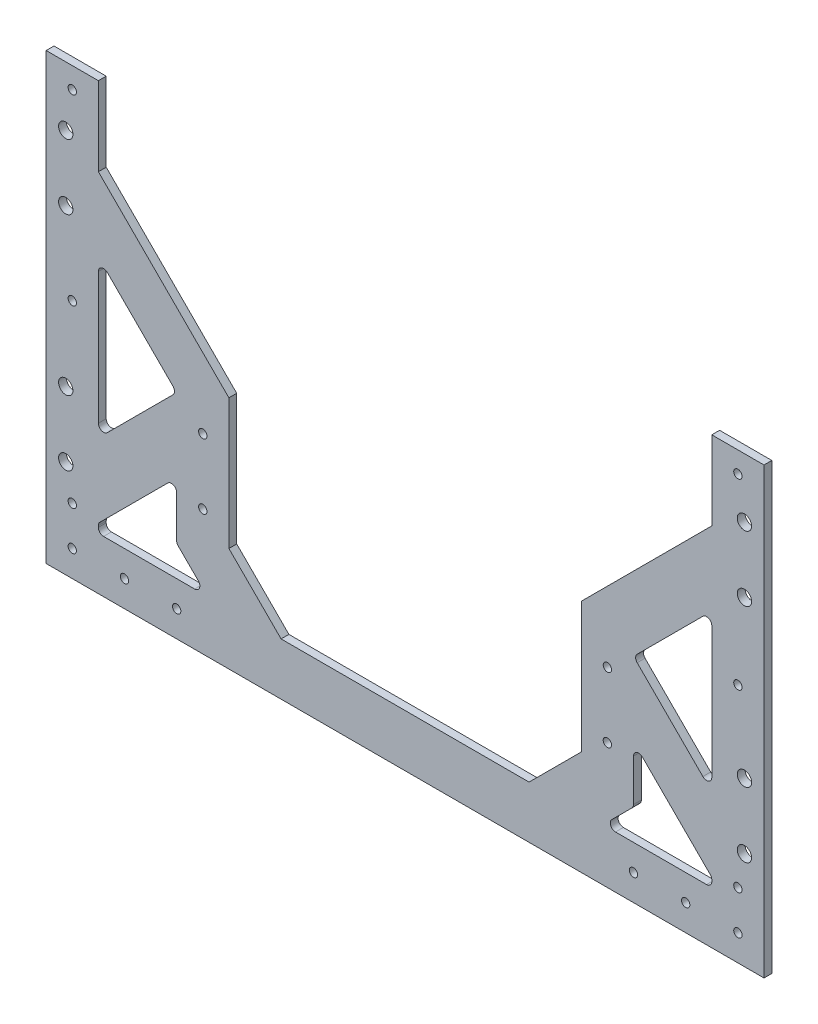
SolidWorks part; units mm, degrees
material "Thornel Mat VMA"
ref_plane "Front Plane" through (0, 0, 0) normal (0, 0, 1) x (1, 0, 0)
ref_plane "Top Plane" through (0, 0, 0) normal (0, 1, 0) x (1, 0, 0)
ref_plane "Right Plane" through (0, 0, 0) normal (1, 0, 0) x (0, 0, -1)
sketch "Sketch1" plane through (0, 0, 0) normal (0, 0, 1) x (1, 0, 0)
  line L0 (-21.5101, 142.7096) -> (-21.5101, -27.503)
  line L1 (-21.5101, 592.497) -> (-21.5101, 302.497) construction
  line L2 (-171.5101, -27.503) -> (403.4899, -27.503) construction
  line L3 (-21.5101, -27.503) -> (253.4899, -27.503)
  line L4 (253.4899, -27.503) -> (253.4899, 142.7096)
  line L5 (253.4899, -7.503) -> (253.4899, 282.497) construction
  line L6 (253.4899, 142.7096) -> (233.4899, 142.7096)
  line L7 (233.4899, -7.503) -> (233.4899, 282.497) construction
  line L8 (233.4899, 142.7096) -> (233.4899, 112.497)
  line L9 (233.4899, 112.497) -> (183.4899, 62.497)
  line L10 (183.4899, 62.497) -> (183.4899, 12.497)
  line L11 (183.4899, 12.497) -> (163.4899, -7.503)
  line L12 (-1.5101, -7.503) -> (233.4899, -7.503) construction
  line L13 (163.4899, -7.503) -> (68.4899, -7.503)
  line L14 (115.9899, -7.503) -> (115.9899, 82.0954) construction
  line L15 (48.4899, 12.497) -> (68.4899, -7.503)
  line L16 (48.4899, 62.497) -> (48.4899, 12.497)
  line L17 (-1.5101, 112.497) -> (48.4899, 62.497)
  line L18 (-1.5101, 142.7096) -> (-1.5101, 112.497)
  line L19 (-21.5101, 142.7096) -> (-1.5101, 142.7096)
  line L20 (-1.5101, 592.497) -> (-1.5101, 302.497) construction
  line L21 (233.4899, -7.503) -> (233.4899, 282.497) construction
  line L22 (-1.5101, -7.503) -> (233.4899, -7.503) construction
  line L23 (-1.5101, -5.503) -> (-1.5101, -4.8999)
  line L24 (1.9041, 80.7986) -> (27.0757, 55.627)
  line L25 (28.4899, 21.1001) -> (28.4899, 5.0412)
  line L26 (29.0757, 3.627) -> (36.7914, -4.0887)
  line L27 (35.3772, -7.503) -> (0.4899, -7.503)
  line L28 (27.0757, 52.7986) -> (1.9041, 27.627)
  line L29 (233.4899, 29.0412) -> (233.4899, 79.3843)
  line L30 (-0.9243, -3.4857) -> (25.0757, 22.5143)
  line L31 (-1.5101, 29.0412) -> (-1.5101, 79.3843)
  line L32 (230.0757, 80.7986) -> (204.9041, 55.627)
  line L33 (232.9041, -3.4857) -> (206.9041, 22.5143)
  line L34 (204.9041, 52.7986) -> (230.0757, 27.627)
  line L35 (196.6026, -7.503) -> (231.4899, -7.503)
  line L36 (202.9041, 3.627) -> (195.1884, -4.0887)
  line L37 (203.4899, 21.1001) -> (203.4899, 5.0412)
  line L38 (233.4899, -5.503) -> (233.4899, -4.8999)
  arc A0 (36.7914, -4.0887) -> (35.3772, -7.503) centre (35.3772, -5.503) cw
  arc A1 (28.4899, 5.0412) -> (29.0757, 3.627) centre (30.4899, 5.0412) ccw
  arc A2 (25.0757, 22.5143) -> (28.4899, 21.1001) centre (26.4899, 21.1001) cw
  arc A3 (-1.5101, 79.3843) -> (1.9041, 80.7986) centre (0.4899, 79.3843) cw
  arc A4 (27.0757, 55.627) -> (27.0757, 52.7986) centre (25.6615, 54.2128) cw
  arc A5 (1.9041, 27.627) -> (-1.5101, 29.0412) centre (0.4899, 29.0412) cw
  arc A6 (-1.5101, -4.8999) -> (-0.9243, -3.4857) centre (0.4899, -4.8999) cw
  arc A7 (-1.5101, -5.503) -> (0.4899, -7.503) centre (0.4899, -5.503) ccw
  arc A8 (233.4899, 79.3843) -> (230.0757, 80.7986) centre (231.4899, 79.3843) ccw
  arc A9 (233.4899, -5.503) -> (231.4899, -7.503) centre (231.4899, -5.503) cw
  arc A10 (233.4899, -4.8999) -> (232.9041, -3.4857) centre (231.4899, -4.8999) ccw
  arc A11 (230.0757, 27.627) -> (233.4899, 29.0412) centre (231.4899, 29.0412) ccw
  arc A12 (204.9041, 55.627) -> (204.9041, 52.7986) centre (206.3183, 54.2128) ccw
  arc A13 (206.9041, 22.5143) -> (203.4899, 21.1001) centre (205.4899, 21.1001) ccw
  arc A14 (203.4899, 5.0412) -> (202.9041, 3.627) centre (201.4899, 5.0412) cw
  arc A15 (195.1884, -4.0887) -> (196.6026, -7.503) centre (196.6026, -5.503) ccw
  point P41 (28.4899, 4.6429)
  point P44 (40.2056, -7.503)
  point P55 (-1.5101, 24.2128)
  point P60 (-1.5101, -7.503)
  dimension "D10" = 2
  dimension "D1" = 20
  dimension "D2" = 45
  dimension "D3" = 50
  dimension "D4" = 20
  dimension "D5" = 50
  dimension "D6" = 20
  dimension "D7" = 20
  dimension "D8" = 20
  dimension "D9" = 45
extrude "Extrude1" add sketch "Sketch1" along normal blind 3
sketch "Sketch2" plane through (0, 0, 3) normal (0, 0, 1) x (1, 0, 0)
  line L0 (-11.5101, 142.7096) -> (-11.5101, -27.503) construction
  line L1 (-1.5101, 142.7096) -> (-21.5101, 142.7096) construction
  line L2 (-21.5101, -27.503) -> (253.4899, -27.503) construction
  line L3 (115.9899, -7.503) -> (115.9899, -27.503) construction
  line L4 (-1.5101, -7.503) -> (233.4899, -7.503) construction
  line L5 (-221.5101, -27.503) -> (453.4899, -27.503) construction
  line L6 (-21.5101, -17.503) -> (115.9899, -17.503) construction
  line L7 (-21.5101, 142.7096) -> (-21.5101, -27.503) construction
  line L8 (68.4899, 20.5695) -> (38.4899, 20.5695) construction
  line L9 (68.4899, 45.5695) -> (38.4899, 45.5695) construction
  line L10 (38.4899, 20.5695) -> (38.4899, 45.5695) construction
  line L11 (48.4899, 12.497) -> (48.4899, 62.497) construction
  circle A0 centre (245.9899, 9.9974) radius 2.75 construction
  circle A1 centre (245.9899, 34.9974) radius 2.75 construction
  circle A2 centre (245.9899, 94.9974) radius 2.75 construction
  circle A3 centre (245.9899, 119.9974) radius 2.75 construction
  circle A4 centre (-14.0101, 9.9974) radius 2.75 construction
  circle A5 centre (-14.0101, 34.9974) radius 2.75 construction
  circle A6 centre (-14.0101, 94.9974) radius 2.75 construction
  circle A7 centre (-14.0101, 119.9974) radius 2.75 construction
  circle A8 centre (245.9899, 9.9974) radius 2.75
  circle A9 centre (245.9899, 34.9974) radius 2.75
  circle A10 centre (245.9899, 94.9974) radius 2.75
  circle A11 centre (245.9899, 119.9974) radius 2.75
  circle A12 centre (-14.0101, 9.9974) radius 2.75
  circle A13 centre (-14.0101, 34.9974) radius 2.75
  circle A14 centre (-14.0101, 94.9974) radius 2.75
  circle A15 centre (-14.0101, 119.9974) radius 2.75
  circle A16 centre (-11.5101, 134.7096) radius 1.6
  circle A17 centre (-11.5101, 64.7096) radius 1.6
  circle A18 centre (-11.5101, -2.503) radius 1.6
  circle A19 centre (-11.5101, -17.503) radius 1.6
  circle A20 centre (8.4899, -17.503) radius 1.6
  circle A21 centre (28.4899, -17.503) radius 1.6
  circle A22 centre (203.4899, -17.503) radius 1.6
  circle A23 centre (223.4899, -17.503) radius 1.6
  circle A24 centre (243.4899, -17.503) radius 1.6
  circle A25 centre (243.4899, -2.503) radius 1.6
  circle A26 centre (243.4899, 64.7096) radius 1.6
  circle A27 centre (243.4899, 134.7096) radius 1.6
  circle A28 centre (245.9899, 119.9974) radius 2.75
  circle A29 centre (245.9899, 94.9974) radius 2.75
  circle A30 centre (245.9899, 34.9974) radius 2.75
  circle A31 centre (245.9899, 9.9974) radius 2.75
  circle A32 centre (38.4899, 20.5695) radius 1.6
  circle A33 centre (38.4899, 45.5695) radius 1.6
  circle A34 centre (193.4899, 45.5695) radius 1.6
  circle A35 centre (193.4899, 20.5695) radius 1.6
  point P82 (0, 0)
  point P83 (0, 0)
  dimension "D1" = 3.2
  dimension "D3" = 70
  dimension "D4" = 15
  dimension "D5" = 20
  dimension "D6" = 20
  dimension "D8" = 3.2
  dimension "D2" = 8
  dimension "D7" = 10
extrude "Cut-Extrude1" cut sketch "Sketch2" against normal blind 3 contours A15 | A14 | A13 | A12 | A18 | A19 | A20 | A21 | A32 | A33 | A17 | A34 | A35 | A22 | A23 | A24 | A9 | A8 | A26 | A27 | A11 | A10 | A16 | A25 region at (245.9899, 9.9974, 3) region at (245.9899, 34.9974, 3) region at (245.9899, 94.9974, 3) region at (245.9899, 119.9974, 3) region at (-14.0101, 9.9974, 3) region at (-14.0101, 34.9974, 3) region at (-14.0101, 94.9974, 3) region at (-14.0101, 119.9974, 3) region at (-11.5101, 64.7096, 3) region at (-11.5101, -2.503, 3) region at (-11.5101, -17.503, 3) region at (8.4899, -17.503, 3) region at (28.4899, -17.503, 3) region at (203.4899, -17.503, 3) region at (223.4899, -17.503, 3) region at (243.4899, -17.503, 3) region at (243.4899, 64.7096, 3) region at (243.4899, 134.7096, 3) region at (38.4899, 20.5695, 3) region at (38.4899, 45.5695, 3) region at (193.4899, 45.5695, 3) region at (193.4899, 20.5695, 3)
